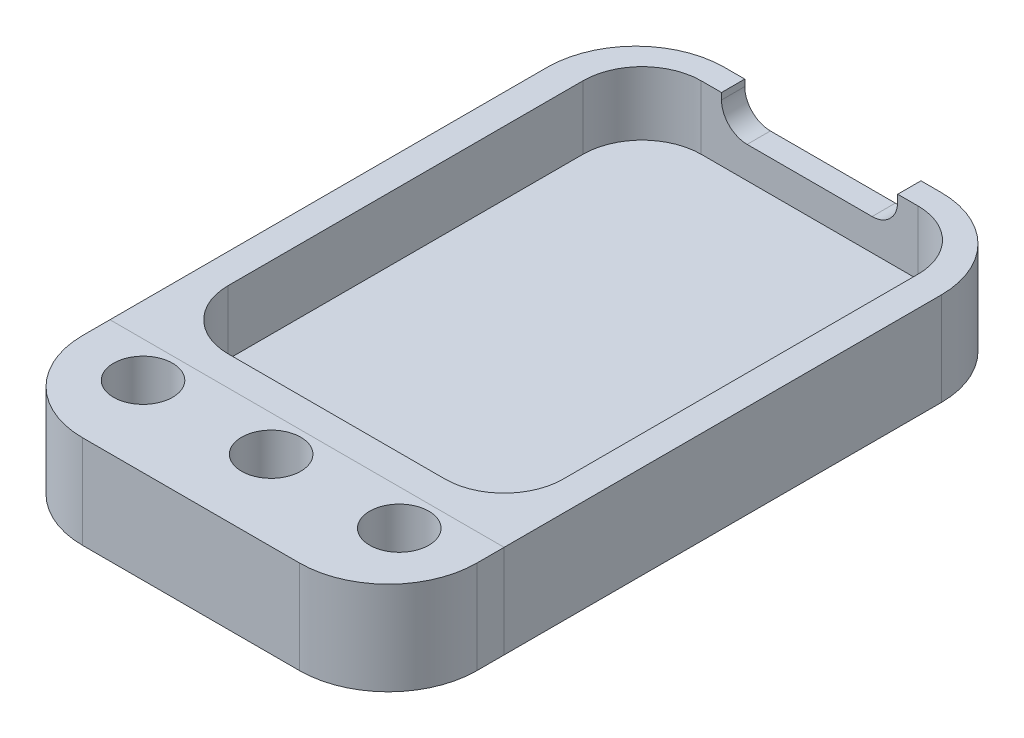
SolidWorks part; units mm, degrees
ref_plane "Front Plane" through (0, 0, 0) normal (0, 0, 1) x (1, 0, 0)
ref_plane "Top Plane" through (0, 0, 0) normal (0, 1, 0) x (1, 0, 0)
ref_plane "Right Plane" through (0, 0, 0) normal (1, 0, 0) x (0, 0, -1)
sketch "Sketch1" plane through (0, 0, 0) normal (0, 1, 0) x (1, 0, 0)
  line L1 (3, 0) -> (14, 0)
  line L2 (0, 3) -> (0, 21)
  line L3 (3, 24) -> (14, 24)
  line L4 (17, 3) -> (17, 21)
  line L5 (18.5, 2.68) -> (18.5, 20.68)
  line L7 (-1.5, 3) -> (-1.5, 21)
  line L11 (18.5, -1.5) -> (18.5, 2.68)
  line L13 (-1.5, 3) -> (-1.5, -1.5)
  line L18 (-1.5, -1.5) -> (18.5, -1.5)
  line L19 (-1.5, 21) -> (-1.5, 25.18)
  line L22 (18.5, 25.18) -> (18.5, 20.68)
  line L23 (-1.5, 25.18) -> (18.5, 25.18)
  arc A0 (17, 21) -> (14, 24) centre (14, 21) ccw
  arc A1 (14, 0) -> (17, 3) centre (14, 3) ccw
  arc A2 (0, 3) -> (3, 0) centre (3, 3) ccw
  arc A3 (0, 21) -> (3, 24) centre (3, 21) cw
  point P7 (17, 24)
  point P10 (17, 0)
  point P13 (0, 0)
  point P16 (0, 24)
  dimension "D3" = 3
  dimension "D1" = 17
  dimension "D2" = 24
  dimension "D5" = 1.5
sketch "Sketch6" plane through (0, 0, 0) normal (0, 1, 0) x (1, 0, 0)
  line L5 (18.5, 2.68) -> (18.5, 20.68)
  line L7 (-1.5, 3) -> (-1.5, 21)
  line L15 (-1.5, 3) -> (-1.5, -1.5)
  line L19 (18.5, 2.68) -> (18.5, -1.5)
  line L23 (-1.5, -1.5) -> (18.5, -1.5)
  line L24 (-1.5, 21) -> (-1.5, 25.18)
  line L27 (18.5, 25.18) -> (18.5, 20.68)
  line L28 (-1.5, 25.18) -> (18.5, 25.18)
extrude "Boss-Extrude3" add sketch "Sketch1" along normal blind 3.23
extrude "Boss-Extrude4" add sketch "Sketch6" against normal blind 1.5
ref_plane "Plane1" through (0, 0, -25.18) normal (0, 0, -1) x (-1, 0, 0)
sketch "Sketch7" plane through (0, 0, -25.18) normal (0, 0, -1) x (-1, 0, 0)
  line L0 (-12.97, 3.23) -> (-4.03, 3.23)
  line L2 (-11.67, 1.6) -> (-5.33, 1.6)
  line L3 (-8.5, 3.23) -> (-8.5, -0.03) construction
  line L4 (-12.97, 3.23) -> (-12.97, 2.9)
  line L5 (-4.03, 3.23) -> (-4.03, 2.9)
  arc A0 (-11.67, 1.6) -> (-12.97, 2.9) centre (-11.67, 2.9) cw
  arc A1 (-5.33, 1.6) -> (-4.03, 2.9) centre (-5.33, 2.9) ccw
  point P4 (-8.5, 3.23)
  point P8 (-8.5, 1.6)
  dimension "D6" = 1.3
  dimension "D1" = 1.63
  dimension "D2" = 8.94
  dimension "D4" = 6.34
  dimension "D5" = 0
extrude "Cut-Extrude1" cut sketch "Sketch7" against normal blind 1.5 and the other way through all
sketch "Sketch10" plane through (0, 0, 0) normal (0, 1, 0) x (1, 0, 0)
  line L4 (18.5, -1.5) -> (18.5, -2.88)
  line L5 (8.5, -8.56) -> (8.5, -1.5) construction
  line L6 (-1.5, -2.88) -> (-1.5, -1.5)
  line L7 (-1.5, 25.18) -> (-1.5, -1.5) construction
  line L8 (-1.5, -1.5) -> (18.5, -1.5) construction
  line L9 (-1.5, -1.5) -> (18.5, -1.5)
  line L10 (3, -7.38) -> (14, -7.38)
  line L11 (1.7785, 25.18) -> (-1.7785, 25.18) construction
  arc A0 (3, -7.38) -> (-1.5, -2.88) centre (3, -2.88) cw
  arc A1 (14, -7.38) -> (18.5, -2.88) centre (14, -2.88) ccw
  dimension "D3" = 4.5
  dimension "D1" = 32.56
  dimension "D2" = 11
  dimension "D4" = 20
extrude "Boss-Extrude5" add sketch "Sketch10" along normal up to surface (3.23 mm away) and the other way up to surface (1.5 mm away) separate body up to face at (8.5, 3.23, -15.1075) other way up to face at (8.5, -1.5, -11.84)
ref_plane "Plane2" through (0, 3.23, 0) normal (0, 1, 0) x (1, 0, 0)
sketch "Sketch11" plane through (0, 3.23, 0) normal (0, 1, 0) x (1, 0, 0)
  line L0 (8.5, -7.38) -> (8.5, -1.5) construction
  line L2 (14, -7.38) -> (3, -7.38) construction
  line L3 (-1.5, -1.5) -> (18.5, -1.5) construction
  line L4 (-1.5, -2.88) -> (-1.5, -1.5) construction
  circle A0 centre (2, -3.32) radius 1.5
  circle A4 centre (15, -3.32) radius 1.5
  circle A5 centre (8.5, -3.32) radius 1.5
  dimension "D3" = 3
  dimension "D4" = 3
  dimension "D1" = 3.5
  dimension "D2" = 4.06
  dimension "D5" = 0
extrude "Cut-Extrude2" cut sketch "Sketch11" against normal blind 3
ref_plane "Plane3" through (0, 3.23, 0) normal (0, 1, 0) x (1, 0, 0)
sketch "Sketch14" plane through (0, 3.23, 0) normal (0, 1, 0) x (1, 0, 0)
  line L0 (3, 25.18) -> (14, 25.18)
  line L1 (1.7785, 25.18) -> (-1.7785, 25.18) construction
  line L5 (3, -7.38) -> (14, -7.38) construction
  line L6 (-1.5, 20.68) -> (-1.5, 25.18)
  line L7 (-1.5, 25.18) -> (-1.5, -1.5) construction
  line L8 (-1.5, 25.18) -> (3, 25.18)
  line L9 (18.5, 20.68) -> (18.5, 25.18)
  line L10 (18.5, -1.5) -> (18.5, 25.18) construction
  line L11 (18.5, 25.18) -> (14, 25.18)
  arc A0 (3, 25.18) -> (-1.5, 20.68) centre (3, 20.68) ccw
  arc A1 (14, 25.18) -> (18.5, 20.68) centre (14, 20.68) cw
  point P2 (8.5, 25.18)
  point P16 (8.5, -7.38)
  dimension "D4" = 4.5
  dimension "D5" = 4.5
  dimension "D1" = 11
  dimension "D2" = 0
  dimension "D3" = 0
extrude "Cut-Extrude3" cut sketch "Sketch14" against normal through all both and the other way through all contours A0 L8 L6 | L11 A1 L9 region at (17.4948, 3.23, -24.1748) region at (-0.4948, 3.23, -24.1749)
